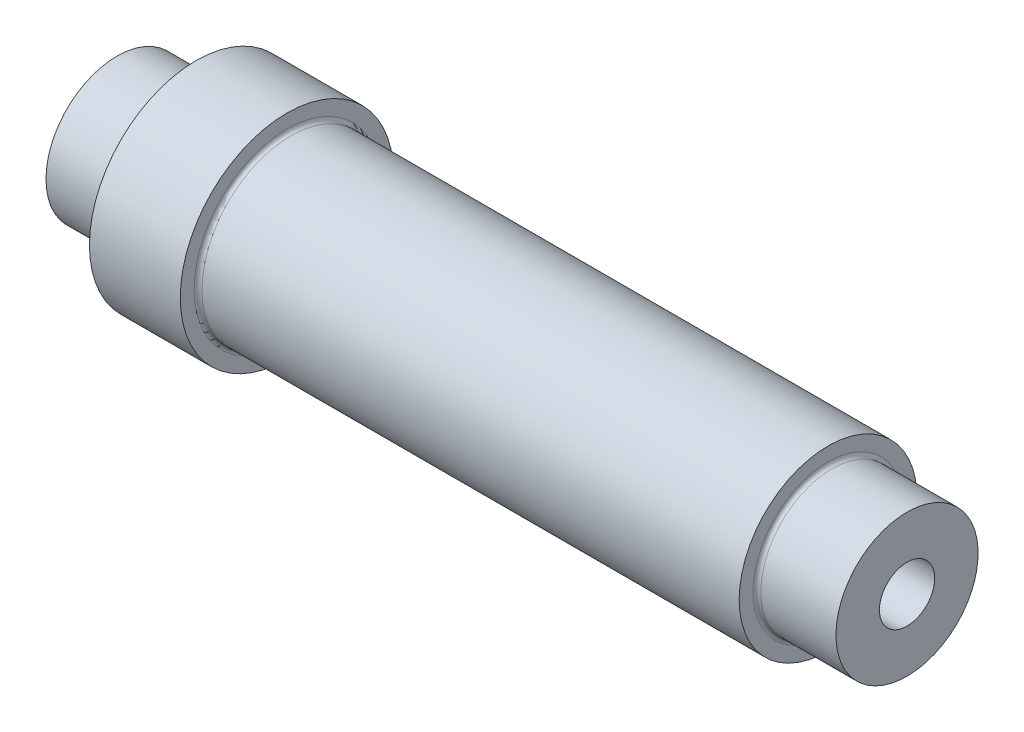
SolidWorks part; units mm, degrees
material "AISI 4340 Aço recozido"
ref_plane "Plano frontal" through (0, 0, 0) normal (0, 0, 1) x (1, 0, 0)
ref_plane "Plano superior" through (0, 0, 0) normal (0, 1, 0) x (1, 0, 0)
ref_plane "Plano direito" through (0, 0, 0) normal (1, 0, 0) x (0, 0, -1)
sketch "Esboço1" plane through (0, 0, 0) normal (0, 0, 1) x (1, 0, 0)
  line L0 (0, 0) -> (57.7383, 0) construction
  line L1 (0, 0) -> (0, 18)
  line L2 (0, 18) -> (20, 18)
  line L3 (20, 18) -> (20, 27)
  line L4 (20, 27) -> (43, 27)
  line L5 (43, 27) -> (43, 22.5)
  line L6 (43, 22.5) -> (180, 22.5)
  line L7 (180, 22.5) -> (180, 18)
  line L8 (180, 18) -> (200, 18)
  line L9 (200, 18) -> (200, 0)
  line L10 (0, 0) -> (200, 0)
  dimension "D1" = 45
  dimension "D2" = 160
  dimension "D3" = 36
  dimension "D4" = 20
  dimension "D5" = 54
  dimension "D6" = 23
revolve "Revolução1" add sketch "Esboço1" angle 360 about L0
hole_wizard "Broca de rosquear para tarraxa de M161" positions "3DSketch1" profile "Esboço2" hole size "M16" standard "ISO"
sketch3d "3DSketch1"
  point P0 (200, 0, 0)
  point P20 (0, 0, 0)
sketch "Esboço2" plane through (200, 0, 0) normal (0, 1, 0) x (0, 0, -1)
  line L0 (0, 0) -> (0, 34.206)
  line L1 (0, 34.206) -> (7, 30)
  line L2 (7, 30) -> (7, 0)
  line L5 (7, 0) -> (0, 0)
  line L10 (0, 34.206) -> (-7, 30) construction
  line L11 (0, -6.35) -> (0, 107.95) construction
  dimension "Hole Dia." = 14
  dimension "Hole Depth" = 30
  dimension "Drill Angle" = 118
fillet "Filete1" radius 1 3 edges at (20, 0, 18) (180, 0, 18) (43, 0, 22.5)
equation "\"escala\"= 1                        'projeto - escala geral"
equation "\"escala_disco-arma\"= 3                                                                  'disco arma - escala geometria disco arma"
equation "\"arma_eixo-furo_folga\"= 4                                                              'disco arma - folga entre furo arma e eixo"
equation "\"arma_rebaixo-camisa_raio\"= 12                                                         'disco arma - raio do rebaixo da camisa da arma "
equation "\"arma_rebaixo-camisa_b\"= \"rolamento_b-esp\" + (\"arma-espessura\"-\"rolamento_b-esp\")/2     'disco arma - profundidade rebaixo camisa"
equation "\"arma-espessura\"= 50                                                                    'disco arma - espessura disco arma"
equation "\"rolamento_D-ext\"= 85               'rolamento arma - diametro externo"
equation "\"rolamento_D1-ext\"= 75             'rolamento arma - ressalto diam externo"
equation "\"rolamento_d-int\"= 45               'rolamento arma - diametro interno"
equation "\"rolamento_b-esp\"= 23               'rolamento arma - espessura"
equation "\"camisa_largura\"=115                                                        'camisa arma - tamanho do lado"
equation "\"camisa_raio\"= 16                                                           'camisa arma - raio canto interno"
equation "\"camisa_raio-alivio\"= 6                                                    'camisa arma - raio de alivio de tensoes no encaixe da arma"
equation "\"camisa_rebaixo_rolamento\"= 1 * \"rolamento_b-esp\""
equation "\"camisa_comprimento-centro\"= 2*(\"arma_rebaixo-camisa_b\")+\"polia_espessura\" "
equation "\"camisa_furos_dist\"= 83"
equation "\"camisa_furos_prof\"= 30"
equation "\"polia_espessura\"= 40  "
equation "\"polia_diam_eff\"= 142"
equation "\"eixo-arm_diam\"= \"rolamento_d-int\"                                                                'eixo arma - diametro"
equation "\"D1@Esboço1\"=\"eixo-arm_diam\""
equation "\"D2@Esboço1\"=\"eixo-arm_comp-entre-mancais\""
equation "\"eixo-arm_comp-espacador\"= \"eixo-arm_folga_mancal-arma\" + \"arma-espessura\"-\"arma_rebaixo-camisa_b\" - \"eixo-arm_allowable-movement\"/2"
equation "\"mancal-arm_rebaixo-eixo_profundidade\"= 20"
equation "\"D3@Esboço1\"=\"mancal-arm_rebaixo-eixo_diametro\""
equation "\"D4@Esboço1\"=\"mancal-arm_rebaixo-eixo_profundidade\""
equation "\"D5@Esboço1\" = \"rolamento_d2-int\""
equation "\"D6@Esboço1\"=\"eixo-arm_comp-espacador\""
equation "\"eixo-arm_prof-furo-fix\"= 30"
equation "\"rolamento_d2-int\"= 54             'rolamento arma - ressalto diam interno"
equation "\"mancal-arm_rebaixo-eixo_diametro\"= 2 * \"eixo-arm_diam\" - \"rolamento_d2-int\""
equation "\"eixo-arm_folga_mancal-arma\"= 10"
equation "\"eixo-arm_allowable-movement\"= 1"
equation "\"eixo-arm_comp-entre-mancais\"= 2*\"eixo-arm_folga_mancal-arma\" + 2*\"arma-espessura\" + \"polia_espessura\"    'eixo arma - comprimento entre mancais"
